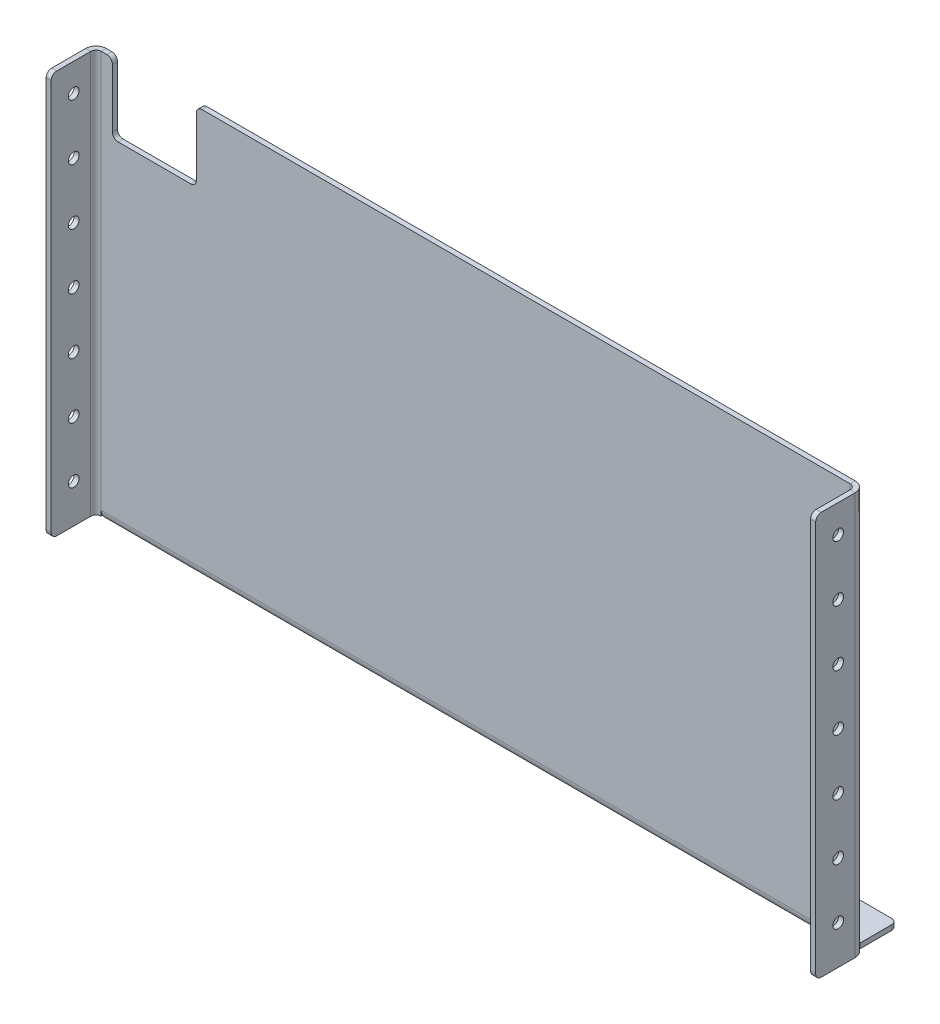
SolidWorks part; units mm, degrees
note: The reader was unsure of these and kept them because the rebuilt part matched: flange length of "Edge-Flange1", "Edge-Flange2".
ref_plane "Front Plane" through (0, 0, 0) normal (0, 0, 1) x (1, 0, 0)
ref_plane "Top Plane" through (0, 0, 0) normal (0, 1, 0) x (1, 0, 0)
ref_plane "Right Plane" through (0, 0, 0) normal (1, 0, 0) x (0, 0, -1)
sketch "Sketch1" plane through (0, 0, 0) normal (0, 0, 1) x (1, 0, 0)
  line L1 (-172.314, -91.357) -> (172.314, -91.357)
  line L2 (-172.314, -91.357) -> (-172.314, 91.357)
  line L3 (-172.314, 91.357) -> (172.314, 91.357)
  line L4 (172.314, -91.357) -> (172.314, 91.357)
  line L5 (-172.314, -91.357) -> (172.314, 91.357) construction
  line L6 (-172.314, 91.357) -> (172.314, -91.357) construction
  point P0 (0, 0)
  dimension "D1" = 344.628
  dimension "D2" = 182.714
base flange "Base-Flange1" sketch "Sketch1" thickness 2.286 reverse thickness direction no parameters "D1"=2.3813
edge flange "Edge-Flange1" sketch "Sketch10" flange profiles "Sketch10", "Sketch11" flange angle 90 flange length 20.32 flange position material outside bend radius 2.3813 thickness 2.286 relief rectangular parameters "D6"=10, "D8"=1
sketch "Sketch10" plane through (172.314, 0, 0) normal (1, 0, 0) x (0, 1, 0)
  line L0 (-91.357, 0) -> (91.357, 0) construction
  line L1 (-91.357, 0) -> (91.357, 0)
  line L2 (-91.357, 0) -> (-91.357, 20.32)
  line L3 (-91.357, 20.32) -> (91.357, 20.32)
  line L4 (91.357, 20.32) -> (91.357, 0)
sketch "Sketch11" plane through (-172.314, 0, 0) normal (-1, 0, 0) x (0, -1, 0)
  line L0 (-91.357, 0) -> (91.357, 0) construction
  line L1 (-91.357, 0) -> (91.357, 0)
  line L2 (-91.357, 0) -> (-91.357, 20.32)
  line L3 (-91.357, 20.32) -> (91.357, 20.32)
  line L4 (91.357, 20.32) -> (91.357, 0)
bend "EdgeBend1" bend radius 2.3813 bend angle 90 parameters "D5"=1
bend "EdgeBend2" bend radius 2.3813 bend angle 90 parameters "D5"=2
edge flange "Edge-Flange2" sketch "Sketch16" flange angle 90 flange length 19.05 flange position material outside bend radius 2.3813 thickness 2.286 relief none parameters "D1"=0.7366, "D6"=10
sketch "Sketch16" plane through (0, -91.357, -2.286) normal (0, -1, 0) x (-1, 0, 0)
  line L2 (-169.9328, 0) -> (-169.9328, 19.05)
  line L3 (-169.9328, 19.05) -> (169.9328, 19.05)
  line L4 (169.9328, 19.05) -> (169.9328, 0)
  line L7 (169.9328, 0) -> (-169.9328, 0) construction
  line L8 (169.9328, 0) -> (-169.9328, 0)
bend "EdgeBend3" bend radius 2.3813 bend angle 90 parameters "D5"=3
sketch "Sketch17" plane through (0, 0, -2.286) normal (0, 0, -1) x (-1, 0, 0)
  line L0 (-169.9328, 91.357) -> (169.9328, 91.357) construction
  line L1 (164.8528, 91.357) -> (126.7528, 91.357)
  line L2 (164.8528, 91.357) -> (164.8528, 59.607)
  line L3 (164.8528, 59.607) -> (126.7528, 59.607)
  line L4 (126.7528, 91.357) -> (126.7528, 59.607)
  line L5 (169.9328, -88.9758) -> (169.9328, 91.357) construction
  dimension "D1" = 31.75
  dimension "D2" = 38.1
  dimension "D3" = 5.08
extrude "Cut-Extrude1" cut sketch "Sketch17" against normal through all normal cut yes
fillet "Fillet1" radius 2.54 10 edges at (-126.7528, 59.607, -1.143) (-164.8528, 59.607, -1.143) (-173.457, -91.357, 20.32) (173.457, 91.357, 20.32) (173.457, -91.357, 20.32) (169.9328, -92.5, -21.336) (-169.9328, -92.5, -21.336) (-173.457, 91.357, 20.32) (-126.7528, 91.357, -1.143) (-164.8528, 91.357, -1.143)
sketch "Sketch18" plane through (-174.6, 0, 0) normal (-1, 0, 0) x (0, 0, 1)
  line L0 (10.0806, 91.357) -> (10.0806, -91.357)
  line L1 (17.78, 91.357) -> (2.3813, 91.357) construction
  line L2 (2.3813, -91.357) -> (17.78, -91.357) construction
  point P6 (10.0806, 78.657)
  point P9 (10.0806, 53.257)
  point P10 (10.0806, 27.857)
  point P11 (10.0806, 2.457)
  point P12 (10.0806, -22.943)
  point P13 (10.0806, -48.343)
  point P14 (10.0806, -73.743)
  dimension "D1" = 12.7
  dimension "D2" = 7
hole_wizard "#11 (0.191) Diameter Hole1" positions "Sketch18" profile "Sketch19" hole size "#11" standard "ANSI Inch"
sketch "Sketch19" plane through (-174.6, -73.743, 10.0806) normal (0, 1, 0) x (0, 0, 1)
  line L0 (0, 0) -> (0, 350.6575)
  line L1 (0, 350.6575) -> (2.4257, 349.2)
  line L2 (2.4257, 349.2) -> (2.4257, 0)
  line L5 (2.4257, 0) -> (0, 0)
  line L10 (0, 350.6575) -> (-2.4257, 349.2) construction
  line L11 (0, -6.35) -> (0, 107.95) construction
  dimension "Hole Dia." = 4.8514
  dimension "Hole Depth" = 349.2
  dimension "Drill Angle" = 118
sketch "Bend-Lines1" [suppressed] plane through (0, 0, 0) normal (0, 1, 0) x (1, 0, 0)
sketch "Bounding-Box1" [suppressed] plane through (0, 0, 0) normal (0, 1, 0) x (1, 0, 0)
sheet metal parameters "Sheet-Metal1" thickness 2.286 parameters "D1"=0.7366
flat pattern "Flat-Pattern1" [suppressed]
sketch "Bend-Lines2" plane through (0, 0, 0) normal (0, 1, 0) x (1, 0, 0)
sketch3d "Bounding-Box2" [suppressed]
  line L0 (175.26, -101.6, 0) -> (-175.26, -101.6, 0) construction
  line L1 (175.26, 101.6, 0) -> (-175.26, 101.6, 0) construction
  line L2 (175.26, -101.6, 0) -> (175.26, 101.6, 0) construction
  line L3 (-175.26, -101.6, 0) -> (-175.26, 101.6, 0) construction
sheet metal parameters "Sheet-Metal2" thickness 2.286 parameters "D1"=0.7366
flat pattern "Flat-Pattern1"
sketch "Bend-Lines2" plane through (0, 0, 0) normal (0, 0, 1) x (1, 0, 0)
  line L0 (-175.8919, 101.6) -> (-175.8919, -101.6) construction
  line L1 (175.8919, -101.6) -> (175.8919, 101.6) construction
  line L2 (-175.8919, 101.6) -> (-175.8919, -101.6) construction
  line L3 (175.8919, -101.6) -> (175.8919, 101.6) construction
sketch3d "Bounding-Box2" [suppressed]
  line L0 (-191.7638, -101.6, 0) -> (191.7638, -101.6, 0) construction
  line L1 (-191.7638, 101.6, 0) -> (191.7638, 101.6, 0) construction
  line L2 (-191.7638, -101.6, 0) -> (-191.7638, 101.6, 0) construction
  line L3 (191.7638, -101.6, 0) -> (191.7638, 101.6, 0) construction
bend of the flat pattern "Flatten-<EdgeBend1>1"
bend of the flat pattern "Flatten-<EdgeBend2>1"
sheet metal parameters "Sheet-Metal3" thickness 2.286 parameters "D1"=0.7366
flat pattern "Flat-Pattern1"
sketch "Bend-Lines2" plane through (0, 0, 0) normal (0, 0, 1) x (1, 0, 0)
  line L0 (-170.3831, 91.357) -> (-170.3831, -91.357) construction
  line L1 (170.3831, -91.357) -> (170.3831, 91.357) construction
  line L2 (-170.3831, 91.357) -> (-170.3831, -91.357) construction
  line L3 (170.3831, -91.357) -> (170.3831, 91.357) construction
  line L4 (-167.7229, -91.636) -> (167.7229, -91.636) construction
  line L5 (-167.7229, -91.636) -> (167.7229, -91.636) construction
sketch3d "Bounding-Box2" [suppressed]
  line L0 (-190.9821, -110.9649, 0) -> (190.9821, -110.9649, 0) construction
  line L1 (-190.9821, 91.357, 0) -> (190.9821, 91.357, 0) construction
  line L2 (-190.9821, -110.9649, 0) -> (-190.9821, 91.357, 0) construction
  line L3 (190.9821, -110.9649, 0) -> (190.9821, 91.357, 0) construction
bend of the flat pattern "Flatten-<EdgeBend1>1"
bend of the flat pattern "Flatten-<EdgeBend2>1"
bend of the flat pattern "Flatten-<EdgeBend3>1"
sheet metal parameters "Sheet-Metal4" thickness 2.286 parameters "D1"=0.7366
flat pattern "Flat-Pattern1"
sketch "Bend-Lines2" plane through (0, 0, 0) normal (0, 0, 1) x (1, 0, 0)
  line L0 (-172.593, 91.357) -> (-172.593, -91.357) construction
  line L1 (172.593, -91.357) -> (172.593, 91.357) construction
  line L2 (-172.593, 91.357) -> (-172.593, -91.357) construction
  line L3 (172.593, -91.357) -> (172.593, 91.357) construction
  line L4 (-169.9328, -91.636) -> (169.9328, -91.636) construction
  line L5 (-169.9328, -91.636) -> (169.9328, -91.636) construction
sketch3d "Bounding-Box2" [suppressed]
  line L0 (-193.1919, -110.9649, 0) -> (193.1919, -110.9649, 0) construction
  line L1 (-193.1919, 91.357, 0) -> (193.1919, 91.357, 0) construction
  line L2 (-193.1919, -110.9649, 0) -> (-193.1919, 91.357, 0) construction
  line L3 (193.1919, -110.9649, 0) -> (193.1919, 91.357, 0) construction
bend of the flat pattern "Flatten-<EdgeBend1>1"
bend of the flat pattern "Flatten-<EdgeBend2>1"
bend of the flat pattern "Flatten-<EdgeBend3>1"
sheet metal parameters "Sheet-Metal5" thickness 2.286 parameters "D1"=0.7366
flat pattern "Flat-Pattern1"
sketch "Bend-Lines2" plane through (0, 0, 0) normal (0, 0, 1) x (1, 0, 0)
  line L0 (-172.593, 91.357) -> (-172.593, -91.357) construction
  line L1 (172.593, -91.357) -> (172.593, 91.357) construction
  line L2 (-172.593, 91.357) -> (-172.593, -91.357) construction
  line L3 (172.593, -91.357) -> (172.593, 91.357) construction
  line L4 (-169.9328, -91.636) -> (169.9328, -91.636) construction
  line L5 (-169.9328, -91.636) -> (169.9328, -91.636) construction
sketch3d "Bounding-Box2" [suppressed]
  line L0 (-193.1919, -110.9649, 0) -> (193.1919, -110.9649, 0) construction
  line L1 (-193.1919, 91.357, 0) -> (193.1919, 91.357, 0) construction
  line L2 (-193.1919, -110.9649, 0) -> (-193.1919, 91.357, 0) construction
  line L3 (193.1919, -110.9649, 0) -> (193.1919, 91.357, 0) construction
bend of the flat pattern "Flatten-<EdgeBend1>1"
bend of the flat pattern "Flatten-<EdgeBend2>1"
bend of the flat pattern "Flatten-<EdgeBend3>1"
